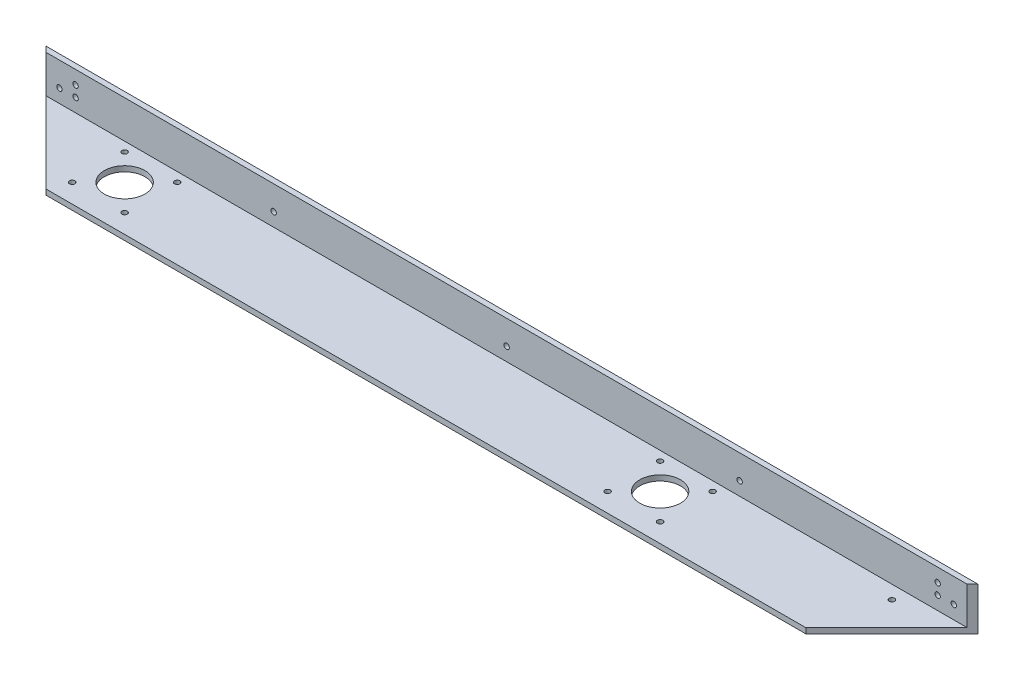
SolidWorks part; units mm, degrees
ref_plane "Front Plane" through (0, 0, 0) normal (0, 0, 1) x (1, 0, 0)
ref_plane "Top Plane" through (0, 0, 0) normal (0, 1, 0) x (1, 0, 0)
ref_plane "Right Plane" through (0, 0, 0) normal (1, 0, 0) x (0, 0, -1)
sketch "Sketch1" plane through (0, 0, 0) normal (1, 0, 0) x (0, 0, -1)
  line L0 (0, 0) -> (-50.8, 0)
  line L1 (-50.8, 0) -> (-50.8, 3.175)
  line L2 (-50.8, 3.175) -> (-3.175, 3.175)
  line L3 (-3.175, 3.175) -> (-3.175, 25.4)
  line L4 (-3.175, 25.4) -> (0, 25.4)
  line L5 (0, 25.4) -> (0, 0)
  dimension "LHeight" = 25.4
  dimension "LWidth" = 50.8
  dimension "LMaterialThickness" = 3.175
  dimension "D1" = 47.625
  dimension "D2" = 22.225
  dimension "D3" = 3.175
extrude "Boss-Extrude1" add sketch "Sketch1" along normal blind 550
chamfer "Chamfer7" distance 50.8 angle 45 1 edges at (0, 1.5875, 50.8)
chamfer "Chamfer8" distance 50.8 angle 45 1 edges at (550, 1.5875, 50.8)
sketch "BotthomHoles-Sketch2" plane through (0, 3.175, 0) normal (0, 1, 0) x (1, 0, 0)
  line L0 (546.825, -3.175) -> (3.175, -3.175) construction
  circle A0 centre (70.575, -24.175) radius 12
  circle A1 centre (386.575, -24.175) radius 12
  circle A2 centre (55.075, -8.675) radius 1.5875
  circle A3 centre (86.075, -8.675) radius 1.5875
  circle A4 centre (371.075, -8.675) radius 1.5875
  circle A5 centre (402.075, -8.675) radius 1.5875
  circle A6 centre (55.075, -39.675) radius 1.5875
  circle A7 centre (86.075, -39.675) radius 1.5875
  circle A8 centre (371.075, -39.675) radius 1.5875
  circle A9 centre (402.075, -39.675) radius 1.5875
  circle A11 centre (510.3125, -11.1125) radius 1.5875
  dimension "D9" = 3.175
  dimension "D10" = 24
  dimension "D2" = 8.675
  dimension "D3" = 31
  dimension "D4" = 15.5
  dimension "D5" = 15.5
  dimension "D6" = 31
  dimension "D7" = 15.5
  dimension "D8" = 31
  dimension "D11" = 21
  dimension "D12" = 316
  dimension "D13" = 70.575
  dimension "D17" = 39.6875
extrude "BottomHoles-Cut-Extrude1" cut sketch "BotthomHoles-Sketch2" against normal through all
sketch "LeftSideHoles-Sketch3" plane through (0, 0, 0) normal (0, 0, -1) x (-1, 0, 0)
  line L0 (0, 0) -> (0, 25.4) construction
  line L1 (-550, 0) -> (-550, 25.4) construction
  line L2 (-550, 25.4) -> (0, 25.4) construction
  circle A1 centre (-529.3625, 17.4625) radius 1.5875
  circle A2 centre (-538.8875, 11.1125) radius 1.5875
  circle A3 centre (-529.3625, 11.1125) radius 1.5875
  circle A4 centre (-11.1125, 11.1125) radius 1.5875
  circle A5 centre (-20.6375, 11.1125) radius 1.5875
  circle A6 centre (-20.6375, 17.4625) radius 1.5875
  circle A8 centre (-412.5, 11.1125) radius 1.5875
  circle A9 centre (-275, 11.1125) radius 1.5875
  circle A10 centre (-137.5, 11.1125) radius 1.5875
  dimension "D7" = 3.175
  dimension "D2" = 20.6375
  dimension "D4" = 11.1125
  dimension "D6" = 20.6375
  dimension "D8" = 137.5
  dimension "D9" = 137.5
  dimension "D10" = 137.5
  dimension "D5" = 11.1125
  dimension "D11" = 11.1125
  dimension "D3" = 7.9375
extrude "LeftSideHoles-Cut-Extrude2" cut sketch "LeftSideHoles-Sketch3" against normal through all
equation "\"LowerRailWidth\"= 2.00in"
equation "\"LowerRailHeight\"= 1.00in"
equation "\"RailThickness\"= .125in'Spec"
equation "\"SideRailHoleY1FromEdge\"= \"HoleOffsetFromEdge\""
equation "\"SideRailHoleX1FromSide\"= \"HoleOffsetFromSide\""
equation "\"StepperHoleDiameter\"= 24mm"
equation "\"StepperMountingHoleDiameter\"= 3.175mm"
equation "\"SideRailLength\"= 550mm"
equation "\"StepperMountingHoleDistance\"= 31mm'Spec"
equation "\"VSWidth\"= 1.25in'Spec"
equation "\"StepperMountingHoleOffsetFromLeftOrRightSide\"= \"StepperMountingHoleOffsetFromItsSide\" + \"RailThickness\""
equation "\"HoleOffsetFromEdge\"= \"RailThickness\" * 2.5"
equation "\"HoleOffsetFromSide\"= \"RailThickness\" * 3.5"
equation "\"StepperMountingHoleOffsetFromItsSide\"= 5.5mm'Spec"
equation "\"SideRailHoleX2FromSide\"= \"VSWidth\" - \"HoleOffsetFromEdge\" - \"RailThickness\"'Equals 20.6375"
equation "\"FasteningHoleDiameter\"= .125in"
equation "\"SideRailHoleY2FromSide\"= \"HoleOffsetFromSide\""
equation "\"LHeight@Sketch1\"=\"LowerRailHeight\""
equation "\"LWidth@Sketch1\"=\"LowerRailWidth\""
equation "\"D1@Chamfer7\"=\"LowerRailWidth\""
equation "\"D1@Chamfer8\"=\"LowerRailWidth\""
equation "\"D2@BotthomHoles-Sketch2\" = \"StepperMountingHoleOffsetFromLeftOrRightSide\""
equation "\"D3@BotthomHoles-Sketch2\" = \"StepperMountingHoleDistance\""
equation "\"D4@BotthomHoles-Sketch2\" = \"StepperMountingHoleDistance\" / 2"
equation "\"D5@BotthomHoles-Sketch2\"= \"StepperMountingHoleDistance\" / 2"
equation "\"D6@BotthomHoles-Sketch2\" = \"StepperMountingHoleDistance\""
equation "\"D7@BotthomHoles-Sketch2\" = \"StepperMountingHoleDistance\" / 2"
equation "\"D8@BotthomHoles-Sketch2\" = \"StepperMountingHoleDistance\""
equation "\"D9@BotthomHoles-Sketch2\" = \"StepperMountingHoleDiameter\""
equation "\"D10@BotthomHoles-Sketch2\" = \"StepperHoleDiameter\""
equation "\"D2@LeftSideHoles-Sketch3\" = \"SideRailHoleX2FromSide\""
equation "\"D4@LeftSideHoles-Sketch3\" = \"SideRailHoleY2FromSide\""
equation "\"D7@LeftSideHoles-Sketch3\" = \"FasteningHoleDiameter\""
equation "\"D1@Boss-Extrude1\"=\"SideRailLength\""
equation "\"D6@LeftSideHoles-Sketch3\"=\"SideRailHoleX2FromSide\""
equation "\"DistanceBetweenFrontToBackStepperHoles\"= \"BedLength\" - \"DistanceFromBedFrontToFirstLeftStepperHole\"'Equals 316"
equation "\"BedThirdSize\"= 70mm"
equation "\"BedLWidth\"= \"BedThirdSize\"'Equals 70"
equation "\"BedInnerSquareWidth\"= \"BedThirdSize\" * 3'Equals 210"
equation "\"BedInnerSquareLength\"= \"BedInnerSquareWidth\""
equation "\"BedLength\" = \"BedInnerSquareLength\" + \"BedLWidth\" * 2 + \"BedIncreasedByLength\"'Equals 350"
equation "\"D12@BotthomHoles-Sketch2\"=\"DistanceBetweenFrontToBackStepperHoles\""
equation "\"DistanceFromFrontSideToFirstLeftStepperHole\"= \"DistanceFromFrontSideToBedFront\" + \"DistanceFromBedFrontToFirstLeftStepperHole\"'Equals 70.575"
equation "\"D13@BotthomHoles-Sketch2\"=\"DistanceFromFrontSideToFirstLeftStepperHole\""
equation "\"DistanceFromBedFrontToFirstLeftStepperHole\"= \"LeadScrewNutPadSize\" + 10mm'Equals 34"
equation "\"DistanceFromFrontSideToBedFront\"= \"RailThickness\" + \"BeltTensionerDepth\" + 10mm'Equals 36.575"
equation "\"BeltTensionerDepth\"= \"BeltTensionerBackWallThickness\" + \"BeltTensionerInnerDepth\"'Equals 23.4"
equation "\"BeltTensionerBackWallThickness\"= 4mm"
equation "\"20TGT2PulleyDiameter\"= 17.9mm'Spec"
equation "\"BeltTensionerSpaceBetweenPulleyAndWall\"= 1.5mm"
equation "\"BeltTensionerInnerDepth\"= \"20TGT2PulleyDiameter\" + \"BeltTensionerSpaceBetweenPulleyAndWall\""
equation "\"BedIncreasedByLength\"= 0mm"
equation "\"LowerCornerBlockWidth\"= \"LowerRailWidth\" - \"RailThickness\" * 2'Room for left front stepper"
equation "\"D17@BotthomHoles-Sketch2\"=\"CornerEnclosureOffset\""
equation "\"CornerEnclosureOffset\"= \"LowerCornerBlockWidth\" - \"HoleOffsetFromEdge\" + \"RailThickness\""
equation "\"LeadScrewNutMountingHoleFlangeDiameter\"= 22mm'Spec"
equation "\"LeadScrewNutPadSize\"= \"LeadScrewNutMountingHoleFlangeDiameter\" + 2mm'Equals 24"
equation "\"LeftOrRightEnclosureOffsets\"= \"SideRailLength\" / 4"
equation "\"D8@LeftSideHoles-Sketch3\"=\"LeftOrRightEnclosureOffsets\""
equation "\"D9@LeftSideHoles-Sketch3\"=\"LeftOrRightEnclosureOffsets\""
equation "\"D10@LeftSideHoles-Sketch3\"=\"LeftOrRightEnclosureOffsets\""
equation "\"D5@LeftSideHoles-Sketch3\"=\"SideRailHoleX1FromSide\""
equation "\"D11@LeftSideHoles-Sketch3\"=\"SideRailHoleX1FromSide\""
equation "\"D3@LeftSideHoles-Sketch3\"=\"SideRailHoleY1FromEdge\""
